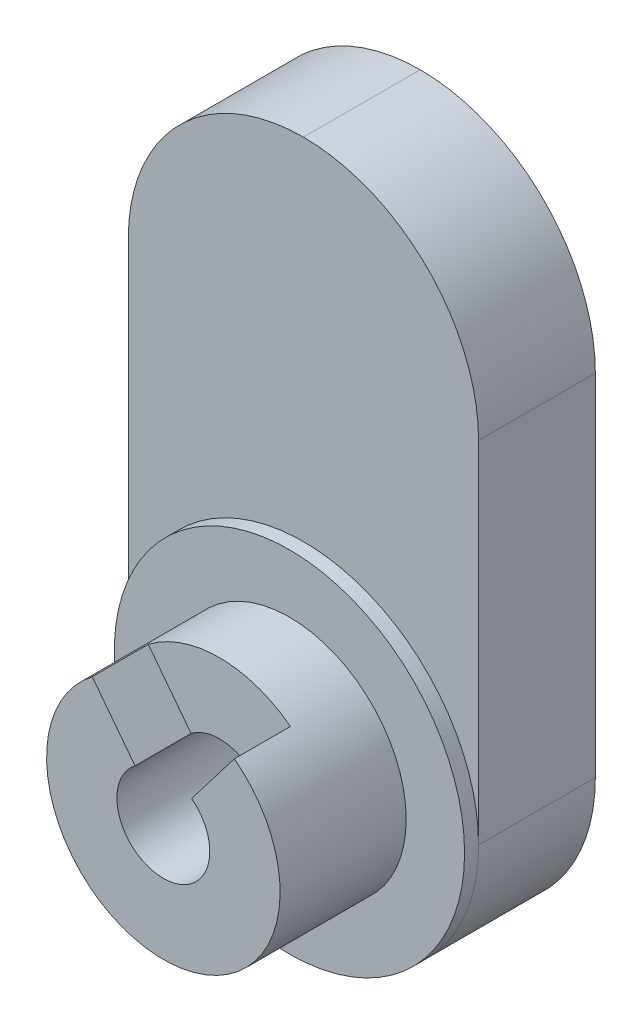
SolidWorks part; units mm, degrees
ref_plane "Front Plane" through (0, 0, 0) normal (0, 0, 1) x (1, 0, 0)
ref_plane "Top Plane" through (0, 0, 0) normal (0, 1, 0) x (1, 0, 0)
ref_plane "Right Plane" through (0, 0, 0) normal (1, 0, 0) x (0, 0, -1)
sketch "Sketch1" plane through (0, 0, 0) normal (0, 0, 1) x (1, 0, 0)
  line L1 (-9.525, 0) -> (9.525, 0)
  line L2 (-9.525, 0) -> (-9.525, 38.1)
  line L3 (-9.525, 38.1) -> (9.525, 38.1)
  line L4 (9.525, 0) -> (9.525, 38.1)
  point P4 (0, 0)
  dimension "D1" = 38.1
  dimension "D2" = 19.05
extrude "Boss-Extrude1" add sketch "Sketch1" along normal blind 6.35
sketch "Sketch2" plane through (0, 0, 6.35) normal (0, 0, 1) x (1, 0, 0)
  line L3 (-9.525, 0) -> (9.525, 0) construction
  circle A0 centre (0, 9.525) radius 6.35
  dimension "D1" = 12.7
  dimension "D2" = 9.525
extrude "Boss-Extrude2" add sketch "Sketch2" along normal blind 7.62
hole_wizard "#8 (0.199) Diameter Hole1" positions "Sketch3" profile "Sketch4" hole size "#8" standard "ANSI Inch" end condition through all
sketch "Sketch3" plane through (0, 0, 13.97) normal (0, 0, 1) x (1, 0, 0)
  circle A0 centre (0, 9.525) radius 6.35 construction
  point P0 (0, 9.525)
sketch "Sketch4" plane through (0, 9.525, 13.97) normal (1, 0, 0) x (0, -1, 0)
  line L0 (0, 0) -> (0, 13.97)
  line L1 (0, 13.97) -> (2.5273, 13.97)
  line L2 (2.5273, 13.97) -> (2.5273, 0)
  line L5 (2.5273, 0) -> (0, 0)
  line L11 (0, -6.35) -> (0, 107.95) construction
  dimension "Thru Hole Dia." = 5.0546
  dimension "Thru Hole Depth" = 13.97
sketch "Sketch5" plane through (0, 0, 0) normal (0, 0, -1) x (-1, 0, 0)
  line L1 (2.3464, 5.461) -> (4.6927, 9.525)
  line L2 (4.6927, 9.525) -> (2.3464, 13.589)
  line L3 (2.3464, 13.589) -> (-2.3464, 13.589)
  line L4 (-2.3464, 13.589) -> (-4.6927, 9.525)
  line L5 (-4.6927, 9.525) -> (-2.3464, 5.461)
  line L6 (-2.3464, 5.461) -> (2.3464, 5.461)
  circle A0 centre (0, 9.525) radius 4.064 construction
  dimension "D1" = 8.128
extrude "Cut-Extrude1" cut sketch "Sketch5" against normal blind 2.54
sketch "Sketch7" plane through (0, 0, 6.35) normal (0, 0, 1) x (1, 0, 0)
  circle A0 centre (0, 9.525) radius 9.525
  circle A1 centre (0, 9.525) radius 6.35
  circle A2 centre (0, 9.525) radius 6.35 construction
  dimension "D1" = 19.05
extrude "Boss-Extrude3" add sketch "Sketch7" along normal blind 0.762
sketch "Sketch8" plane through (0, 0, 13.97) normal (0, 0, 1) x (1, 0, 0)
  line L0 (1.5385, 11.53) -> (3.8656, 14.5628)
  line L1 (-3.8656, 14.5628) -> (-1.5385, 11.53)
  line L2 (-1.5385, 11.53) -> (0, 9.525) construction
  line L3 (0, 9.525) -> (1.5385, 11.53) construction
  arc A0 (3.8656, 14.5628) -> (-3.8656, 14.5628) centre (0, 9.525) ccw
  arc A1 (1.5385, 11.53) -> (-1.5385, 11.53) centre (0, 9.525) ccw
  circle A2 centre (0, 9.525) radius 2.5273 construction
  circle A3 centre (0, 9.525) radius 6.35 construction
  dimension "D1" = 75
extrude "Cut-Extrude2" cut sketch "Sketch8" against normal blind 3.048
fillet "Fillet1" radius 9.525 4 edges at (9.525, 0, 3.175) (-9.525, 0, 3.175) (9.525, 38.1, 3.175) (-9.525, 38.1, 3.175)
